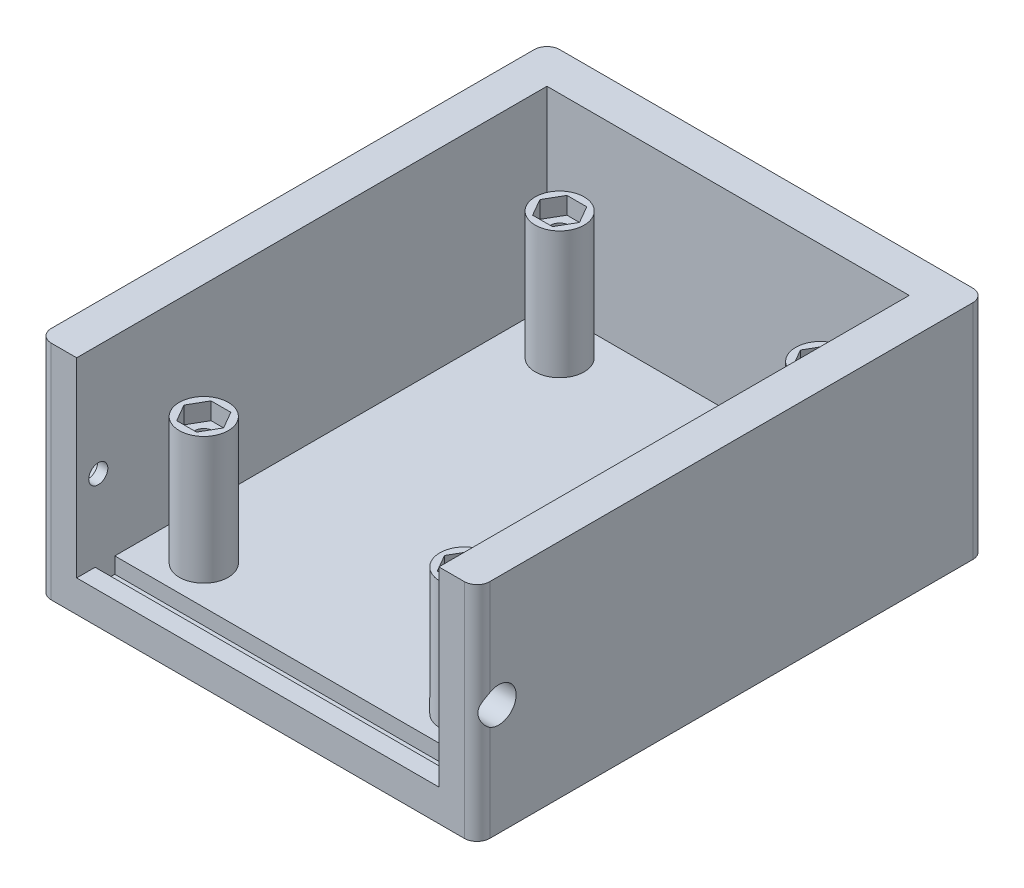
SolidWorks part; units mm, degrees
ref_plane "Front Plane" through (0, 0, 0) normal (0, 0, 1) x (1, 0, 0)
ref_plane "Top Plane" through (0, 0, 0) normal (0, 1, 0) x (1, 0, 0)
ref_plane "Right Plane" through (0, 0, 0) normal (1, 0, 0) x (0, 0, -1)
sketch "Sketch1" plane through (0, 0, 0) normal (0, 1, 0) x (1, 0, 0)
  line L0 (-32.5, 40) -> (32.5, -40) construction
  line L1 (-32.5, -40) -> (32.5, -40)
  line L2 (-32.5, -40) -> (-32.5, 40)
  line L3 (-32.5, 40) -> (32.5, 40)
  line L4 (32.5, -40) -> (32.5, 40)
  line L5 (32.5, 40) -> (-32.5, -40) construction
  point P4 (0, 0)
  dimension "D1" = 65
  dimension "D2" = 80
extrude "Boss-Extrude1" add sketch "Sketch1" along normal blind 5
sketch "Sketch2" plane through (0, 5, 0) normal (0, 1, 0) x (1, 0, 0)
  line L0 (-28.5, 34) -> (28.5, -34) construction
  line L1 (-28.5, -34) -> (28.5, -34)
  line L2 (-28.5, -34) -> (-28.5, 34)
  line L3 (-28.5, 34) -> (28.5, 34)
  line L4 (28.5, -34) -> (28.5, 34)
  line L5 (28.5, 34) -> (-28.5, -34) construction
  line L7 (-32.5, -40) -> (32.5, -40)
  line L8 (-32.5, -40) -> (-32.5, 40)
  line L9 (-32.5, 40) -> (32.5, 40)
  line L10 (32.5, -40) -> (32.5, 40)
  point P4 (0, 0)
  dimension "D1" = 68
  dimension "D2" = 57
extrude "Boss-Extrude2" add sketch "Sketch2" along normal blind 30
sketch "Sketch3" plane through (0, 5, 0) normal (0, 1, 0) x (1, 0, 0)
  line L6 (-20.5, 28) -> (20.5, 28) construction
  line L7 (-20.5, 28) -> (-20.5, -28) construction
  line L8 (-20.5, -28) -> (20.5, -28) construction
  line L9 (20.5, 28) -> (20.5, -28) construction
  line L10 (-20.5, 28) -> (20.5, -28) construction
  line L11 (-20.5, -28) -> (20.5, 28) construction
  circle A0 centre (-20.5, -28) radius 3.85
  circle A1 centre (20.5, -28) radius 3.85
  circle A2 centre (20.5, 28) radius 3.85
  circle A3 centre (-20.5, 28) radius 3.85
  point P1 (0, 0)
  point P4 (0, 0)
  dimension "D5" = 7.7
  dimension "D8" = 7.7
  dimension "D13" = 7.7
  dimension "D16" = 7.7
  dimension "D2" = 56
  dimension "D3" = 41
extrude "Boss-Extrude3" add sketch "Sketch3" along normal blind 20
hole_wizard "Ø3.0mm Dowel Hole1" positions "Sketch10" profile "Sketch5" hole size "Ø3.0" standard "ISO"
sketch "Sketch10" plane through (0, 25, 0) normal (0, 1, 0) x (1, 0, 0)
  point P0 (-20.5, 28)
  point P3 (20.5, 28)
  point P6 (20.5, -28)
  point P9 (-20.5, -28)
sketch "Sketch5" plane through (-20.5, 25, -28) normal (1, 0, 0) x (0, 0, 1)
  line L0 (0, 0) -> (0, 9.4013)
  line L1 (0, 9.4013) -> (1.5, 8.5)
  line L2 (1.5, 8.5) -> (1.5, 0.025)
  line L3 (1.5, 0.025) -> (1.525, 0)
  line L5 (1.525, 0) -> (0, 0)
  line L6 (-1.5, 0.025) -> (-1.525, 0) construction
  line L10 (0, 9.4013) -> (-1.5, 8.5) construction
  line L11 (0, -6.35) -> (0, 107.95) construction
  dimension "Hole Dia." = 3
  dimension "Hole Depth" = 8.5
  dimension "Near C'Sink Dia." = 3.05
  dimension "Near C'Sink Angle" = 90
  dimension "Drill Angle" = 118
sketch "Sketch8" plane through (0, 25, 0) normal (0, 1, 0) x (1, 0, 0)
  line L1 (-17.3823, 28) -> (-18.9412, 30.7)
  line L2 (-18.9412, 30.7) -> (-22.0588, 30.7)
  line L3 (-22.0588, 30.7) -> (-23.6177, 28)
  line L4 (-23.6177, 28) -> (-22.0588, 25.3)
  line L5 (-22.0588, 25.3) -> (-18.9412, 25.3)
  line L6 (-18.9412, 25.3) -> (-17.3823, 28)
  circle A0 centre (-20.5, 28) radius 2.7 construction
  circle A1 centre (-20.5, 28) radius 1.525 construction
  dimension "D1" = 2.7
  dimension "D2" = 3.1177
extrude "Cut-Extrude1" cut sketch "Sketch8" against normal blind 2.7
mirror "Mirror1" about plane through (0, 0, 0) normal (0, 0, 1) of "Cut-Extrude1" second plane through (0, 0, 0) second plane normal (1, 0, 0)
sketch "Sketch13" plane through (32.5, 0, 0) normal (1, 0, 0) x (0, 0, -1)
  line L0 (-40, 17.5) -> (40, 17.5) construction
  line L1 (-40, 35) -> (-40, 0) construction
  line L2 (40, 35) -> (40, 0) construction
  circle A1 centre (-36.6, 17.5) radius 2.75
  dimension "D1" = 5.5
  dimension "D3" = 3.4
extrude "Cut-Extrude4" cut sketch "Sketch13" against normal blind 2.4
sketch "Sketch14" plane through (32.5, 0, 0) normal (1, 0, 0) x (0, 0, -1)
  circle A0 centre (-36.6, 17.5) radius 1.5
extrude "Cut-Extrude5" cut sketch "Sketch14" against normal blind 4
mirror "Mirror2" about plane through (0, 0, 0) normal (1, 0, 0) of "Cut-Extrude5", "Cut-Extrude4"
sketch "Sketch11" plane through (0, 35, 0) normal (0, 1, 0) x (1, 0, 0)
  line L0 (-32.5, -40) -> (32.5, -40) construction
  line L1 (-28.5, -34) -> (28.5, -34)
  line L2 (-28.5, -34) -> (-28.5, -40)
  line L3 (-28.5, -40) -> (28.5, -40)
  line L4 (28.5, -34) -> (28.5, -40)
  line L5 (-28.5, -34) -> (28.5, -40) construction
  line L6 (-28.5, -40) -> (28.5, -34) construction
  line L7 (28.5, -34) -> (28.5, 34) construction
  point P4 (0, -37)
  dimension "D1" = 6
extrude "Cut-Extrude2" cut sketch "Sketch11" against normal blind 30
sketch "Sketch15" plane through (0, 5, 0) normal (0, 1, 0) x (1, 0, 0)
  line L0 (-28.5, 34) -> (-28.5, -40) construction
  line L1 (-28.5, -34) -> (28.5, -34)
  line L2 (-28.5, -34) -> (-28.5, -37.1)
  line L3 (-28.5, -37.1) -> (28.5, -37.1)
  line L4 (28.5, -34) -> (28.5, -37.1)
  line L5 (-28.5, -34) -> (28.5, -37.1) construction
  line L6 (-28.5, -37.1) -> (28.5, -34) construction
  line L7 (28.5, -40) -> (28.5, 34) construction
  line L8 (-28.5, -40) -> (28.5, -40) construction
  point P4 (0, -35.55)
  dimension "D1" = 2.9
  dimension "D2" = 3.1
extrude "Cut-Extrude6" cut sketch "Sketch15" against normal blind 2.5
sketch "Sketch16" plane through (-32.5, 0, 0) normal (-1, 0, 0) x (0, 0, 1)
  line L1 (-40, 35) -> (40, 35)
  line L2 (-40, 35) -> (-40, 0)
  line L3 (-40, 0) -> (40, 0)
  line L4 (40, 35) -> (40, 0)
  line L5 (-40, 35) -> (40, 0) construction
  line L6 (-40, 0) -> (40, 35) construction
  circle A0 centre (36.6, 17.5) radius 2.75
  point P4 (0, 17.5)
  dimension "D1" = 5.5
extrude "Boss-Extrude4" add sketch "Sketch16" along normal blind 2
mirror "Mirror3" about plane through (0, 0, 0) normal (1, 0, 0) of "Boss-Extrude4"
fillet "Fillet1" radius 2 4 edges at (34.5, 17.5, -40) (34.5, 17.5, 40) (-34.5, 17.5, 40) (-34.5, 17.5, -40)
